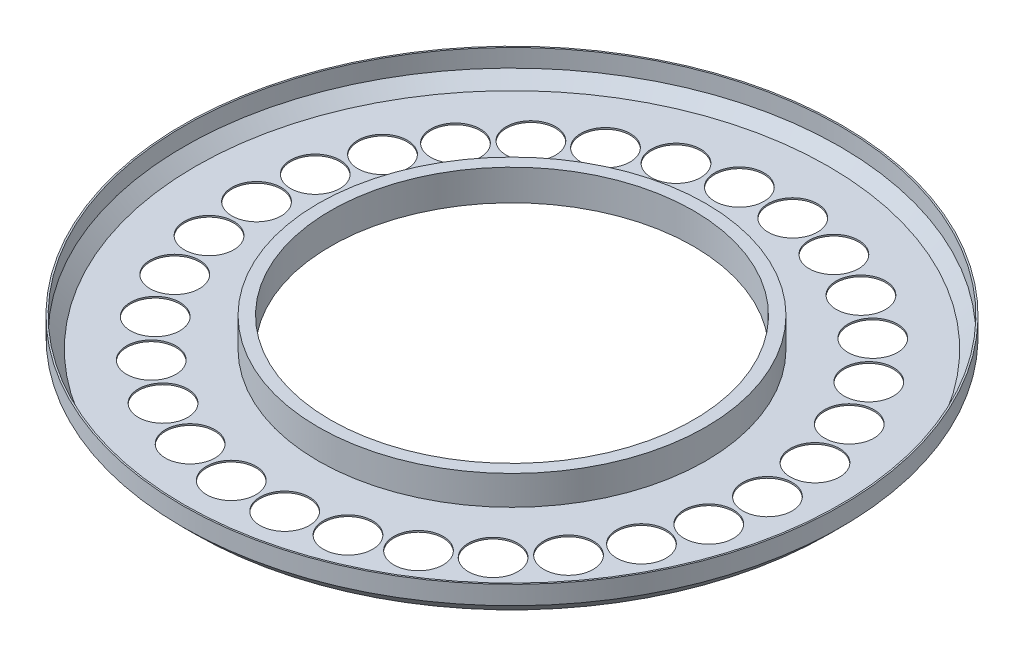
SolidWorks part; units mm, degrees
material "Glass"
ref_plane "Front Plane" through (0, 0, 0) normal (1, 0, 0) x (0, 1, 0)
ref_plane "Top Plane" through (0, 0, 0) normal (0, 0, 1) x (0, 1, 0)
ref_plane "Right Plane" through (0, 0, 0) normal (0, 1, 0) x (-1, 0, 0)
sketch "Sketch1" plane through (0, 0, 0) normal (1, 0, 0) x (0, 1, 0)
  line L0 (0, 18.4828) -> (0, -17.8621) construction
  line L1 (-14.7241, 0) -> (12.5172, 0) construction
  line L2 (0, 53.385) -> (0, 0)
  line L4 (0, 53.385) -> (5, 53.385)
  line L5 (5, 53.385) -> (5, 0)
  line L6 (5, 0) -> (0, 0)
  line L7 (-2.9345, 53.385) -> (0, 53.385) construction
  dimension "D1" = 5
  dimension "D3" = 106.77
revolve "Revolve1" add sketch "Sketch1" angle 360 about L1
chamfer "Chamfer1" distance 2 angle 45 1 edges at (0, 0, -53.385)
shell "Shell1" thickness 0.25 removed face at (0, 5, -53.385)
sketch "Sketch2" plane through (0, 0, 0) normal (0, -1, 0) x (1, 0, 0)
  line L0 (-60.4464, 0) -> (59.601, 0) construction
  circle A4 centre (0, 0) radius 29.385
  circle A5 centre (0, 0) radius 29.385
  circle A6 centre (-41.38, 0) radius 4
  circle A7 centre (0, 0) radius 31.385
  circle A8 centre (0, 0) radius 31.385
  dimension "D3" = 8
  dimension "D4" = 41.38
  dimension "D1" = 24
  dimension "D2" = 20
extrude "Cut-Extrude1" cut sketch "Sketch2" against normal blind 10 contours L0 A5 | A5 L0 region at (0, 0, -12.4714) region at (0, 0, 12.4714)
extrude "Boss-Extrude1" add sketch "Sketch2<3>" against normal up to surface (5 mm away) contours L0 A8 A5 | A8 L0 A5 region at (0, 0, 30.0868) region at (30.385, 0, -0.7018) up to face at (0, 5, -53.135)
sketch "Sketch2<3>" plane through (0, 0, 0) normal (0, -1, 0) x (1, 0, 0) same geometry as "Sketch2"
extrude "Cut-Extrude2" cut sketch "Sketch2<4>" against normal through all both and the other way through all contours A6 L0 | L0 A6 region at (-41.38, 0, -1.6977) region at (-41.38, 0, 1.6977)
sketch "Sketch2<4>" plane through (0, 0, 0) normal (0, -1, 0) x (1, 0, 0) same geometry as "Sketch2"
pattern_circular "CirPattern1" count 30 over 360 about axis through (0, 0, 0) along (0, -1, 0) of "Cut-Extrude2"
